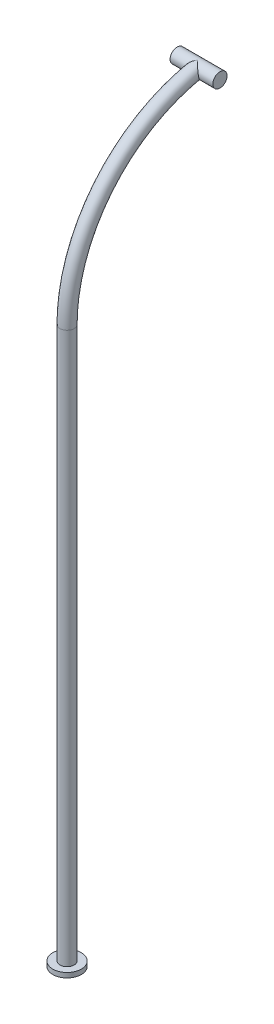
SolidWorks part; units mm, degrees
material "Nylon 101"
ref_plane "Front Plane" through (0, 0, 0) normal (0, 0, 1) x (1, 0, 0)
ref_plane "Top Plane" through (0, 0, 0) normal (0, 1, 0) x (1, 0, 0)
ref_plane "Right Plane" through (0, 0, 0) normal (1, 0, 0) x (0, 0, -1)
sketch "Sketch1" plane through (0, 0, 0) normal (0, 1, 0) x (1, 0, 0)
  circle A0 centre (0, 0) radius 1.5
extrude "Boss-Extrude1" add sketch "Sketch1" along normal blind 116
sketch "Sketch4" plane through (0, 0, 0) normal (0, -1, 0) x (1, 0, 0)
  circle A0 centre (0, 0) radius 3
extrude "Boss-Extrude4" add sketch "Sketch4" along normal blind 1
sketch "Sketch7" plane through (0, 116, 0) normal (0, 1, 0) x (1, 0, 0)
  line L0 (0, 0) -> (0, 44.3626) construction
  line L1 (0, 44.3626) -> (0, 33.5) construction
  line L2 (0, 33.5) -> (-42.5101, 33.5) construction
  line L3 (-42.5101, 33.5) -> (39.1951, 33.5) construction
  circle A0 centre (0, 0) radius 1.5
  dimension "D1" = 33.5
revolve "Revolve1" add sketch "Sketch7" angle 80 about L3 reverse direction yes
sketch "Sketch8" plane through (0, 0, 0) normal (1, 0, 0) x (0, 0, -1)
  line L0 (27.9433, 147.5138) -> (27.4223, 150.4683) construction
  circle A0 centre (27.6828, 148.9911) radius 1.5
extrude "Boss-Extrude5" add sketch "Sketch8" along normal blind 4.5 and the other way blind 4.5
equation "\"4.5.00mm\"=10"
